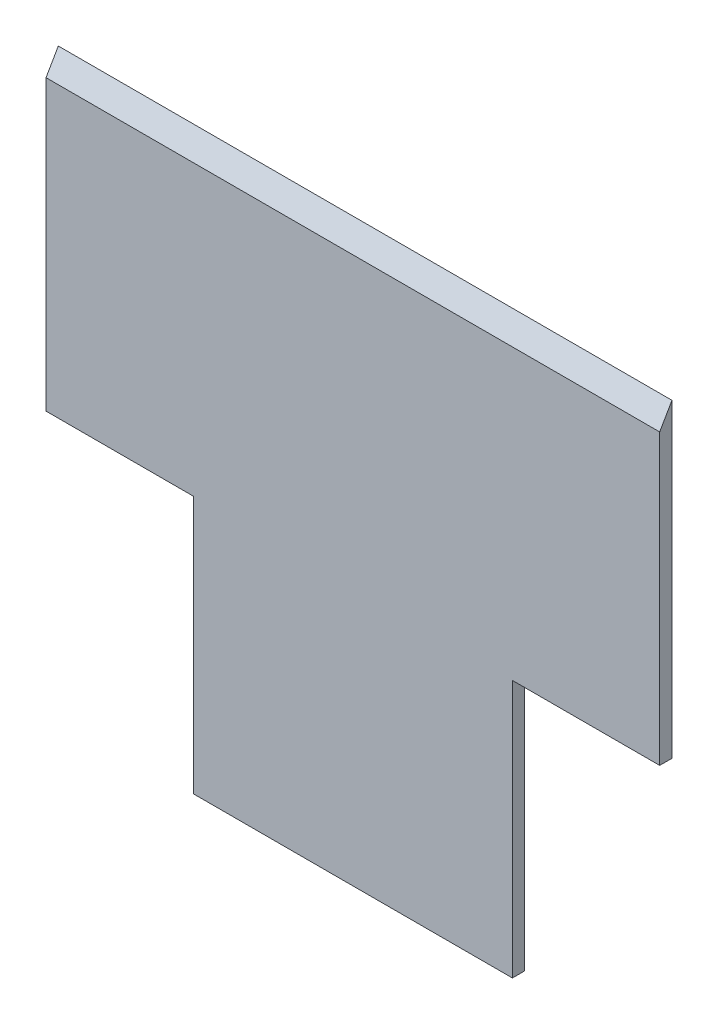
SolidWorks part; units mm, degrees
ref_plane "Alzado" through (0, 0, 0) normal (0, 0, 1) x (1, 0, 0)
ref_plane "Planta" through (0, 0, 0) normal (0, 1, 0) x (1, 0, 0)
ref_plane "Vista lateral" through (0, 0, 0) normal (1, 0, 0) x (0, 0, -1)
sketch "Croquis1" plane through (0, 0, 0) normal (0, 0, 1) x (1, 0, 0)
  line L4 (100, 100) -> (100, 42)
  line L10 (76, 0) -> (24, 0)
  line L11 (24, 42) -> (0, 42)
  line L14 (24, 42) -> (24, 0)
  line L16 (76, 42) -> (76, 0)
  line L17 (0, 42) -> (0, 100)
  line L18 (0, 100) -> (100, 100)
  line L19 (100, 42) -> (76, 42)
extrude "Saliente-Extruir1" add sketch "Croquis1" along normal blind 2
sketch "Croquis4" plane through (0, 0, 0) normal (-1, 0, 0) x (0, 0, 1)
  line L1 (2, 89.0656) -> (2, 91.0656)
  line L2 (2, 93.0667) -> (2, 91.0656)
  line L3 (0, 100) -> (0, 42) construction
  line L4 (2, 91.0656) -> (2, 93.0667) construction
  line L5 (2, 93.0667) -> (2, 100)
  line L7 (2, 42) -> (0, 42) construction
  line L11 (0, 96.5333) -> (0, 94.5322)
  line L13 (2, 100) -> (0, 100)
  line L14 (0, 100) -> (0, 96.5333)
  line L15 (0, 94.5322) -> (0, 92.5322) construction
  line L17 (0, 92.5322) -> (2, 89.0656)
  line L19 (0, 92.5322) -> (0, 94.5322)
  dimension "D1" = 47.0656
  dimension "D2" = 50.5322
  dimension "D3" = 51.0667
extrude "Cortar-Extruir2" cut sketch "Croquis4" against normal up to vertex (100 mm away) up to point (100, 100, 2)
